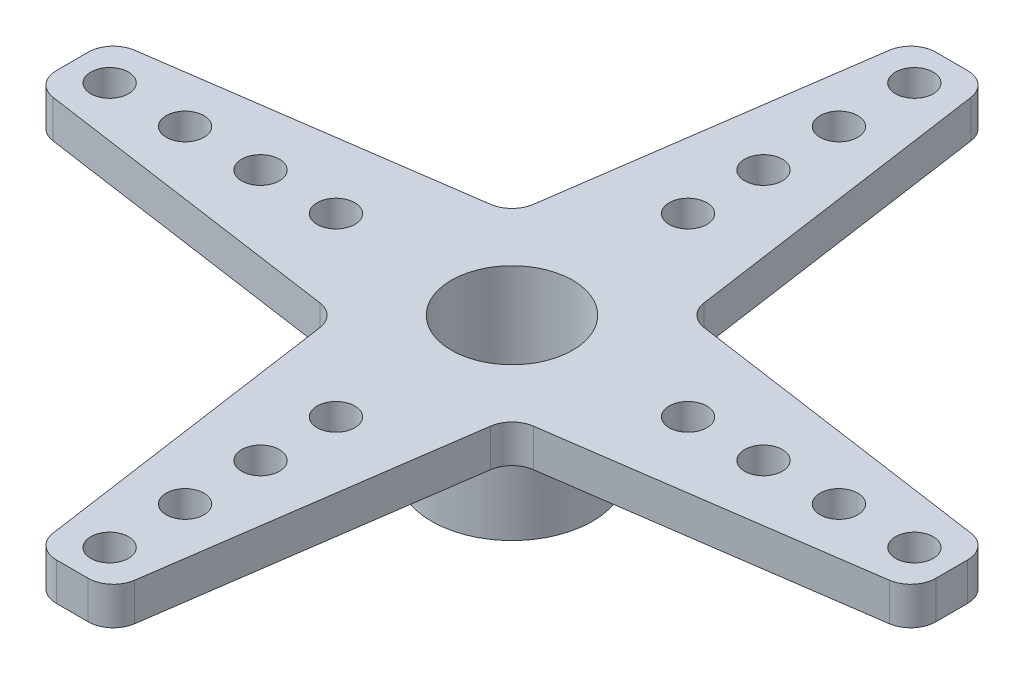
SolidWorks part; units mm, degrees
ref_plane "Front" through (0, 0, 0) normal (0, 0, 1) x (1, 0, 0)
ref_plane "Top" through (0, 0, 0) normal (0, 1, 0) x (1, 0, 0)
ref_plane "Right" through (0, 0, 0) normal (1, 0, 0) x (0, 0, -1)
sketch "Sketch1" plane through (0, 0, 0) normal (0, 1, 0) x (1, 0, 0)
  line L0 (-1.5, 17.4847) -> (-3.5, 3.5)
  line L1 (-3.5, 3.5) -> (-17.4847, 1.5)
  line L2 (-17.4847, 1.5) -> (-17.4847, -1.5)
  line L3 (-17.4847, -1.5) -> (-3.5, -3.5)
  line L4 (-3.5, -3.5) -> (-1.5, -17.4847)
  line L5 (-1.5, -17.4847) -> (1.5, -17.4847)
  line L6 (1.5, -17.4847) -> (3.5, -3.5)
  line L7 (3.5, -3.5) -> (17.4847, -1.5)
  line L8 (17.4847, -1.5) -> (17.4847, 1.5)
  line L9 (17.4847, 1.5) -> (3.5, 3.5)
  line L10 (3.5, 3.5) -> (1.5, 17.4847)
  line L11 (1.5, 17.4847) -> (-1.5, 17.4847)
  circle A0 centre (0, 0) radius 2.413
  circle A1 centre (7, 0) radius 0.75
  circle A2 centre (10, 0) radius 0.75
  circle A3 centre (13, 0) radius 0.75
  circle A4 centre (16, 0) radius 0.75
  circle A5 centre (0, -7) radius 0.75
  circle A6 centre (0, -10) radius 0.75
  circle A7 centre (0, -13) radius 0.75
  circle A8 centre (0, -16) radius 0.75
  circle A9 centre (-7, 0) radius 0.75
  circle A10 centre (-10, 0) radius 0.75
  circle A11 centre (-13, 0) radius 0.75
  circle A12 centre (-16, 0) radius 0.75
  circle A13 centre (0, 7) radius 0.75
  circle A14 centre (0, 10) radius 0.75
  circle A15 centre (0, 13) radius 0.75
  circle A16 centre (0, 16) radius 0.75
  point P38 (0, 0)
  point P42 (-3.361, 17.2154)
  point P49 (0, 17.4847)
  point P50 (-17.4847, 0)
  point P51 (-19.3502, 2.7585)
  point P52 (-7, 7)
  point P53 (-8.7484, 4.966)
  point P54 (-4.8303, 20.0801)
  point P55 (0, 0)
  point P56 (0, 0)
  point P57 (-3.8273, 2.6919)
  point P58 (-17.4847, 1.6926)
  point P59 (-3.6593, 3.6593)
  dimension "D5" = 1.5
  dimension "D6" = 4.826
  dimension "D1" = 7
  dimension "D2" = 10
  dimension "D3" = 13
  dimension "D4" = 16
  dimension "D8" = 17.4847
  dimension "D9" = 3
  dimension "D10" = 7
  dimension "D7" = 4
extrude "Boss-Extrude1" add sketch "Sketch1" along normal blind 1.5
sketch "Sketch2" plane through (0, 0, 0) normal (0, -1, 0) x (1, 0, 0)
  circle A0 centre (0, 0) radius 3.2
  circle A1 centre (0, 0) radius 2.413
  circle A2 centre (0, 0) radius 2.413 construction
  dimension "D1" = 6.4
extrude "Boss-Extrude2" add sketch "Sketch2" along normal blind 4
fillet "Fillet1" radius 1 12 edges at (-3.5, 0.75, -3.5) (-1.5, 0.75, -17.4847) (1.5, 0.75, -17.4847) (3.5, 0.75, -3.5) (17.4847, 0.75, -1.5) (17.4847, 0.75, 1.5) (3.5, 0.75, 3.5) (1.5, 0.75, 17.4847) (-1.5, 0.75, 17.4847) (-3.5, 0.75, 3.5) (-17.4847, 0.75, -1.5) (-17.4847, 0.75, 1.5)
